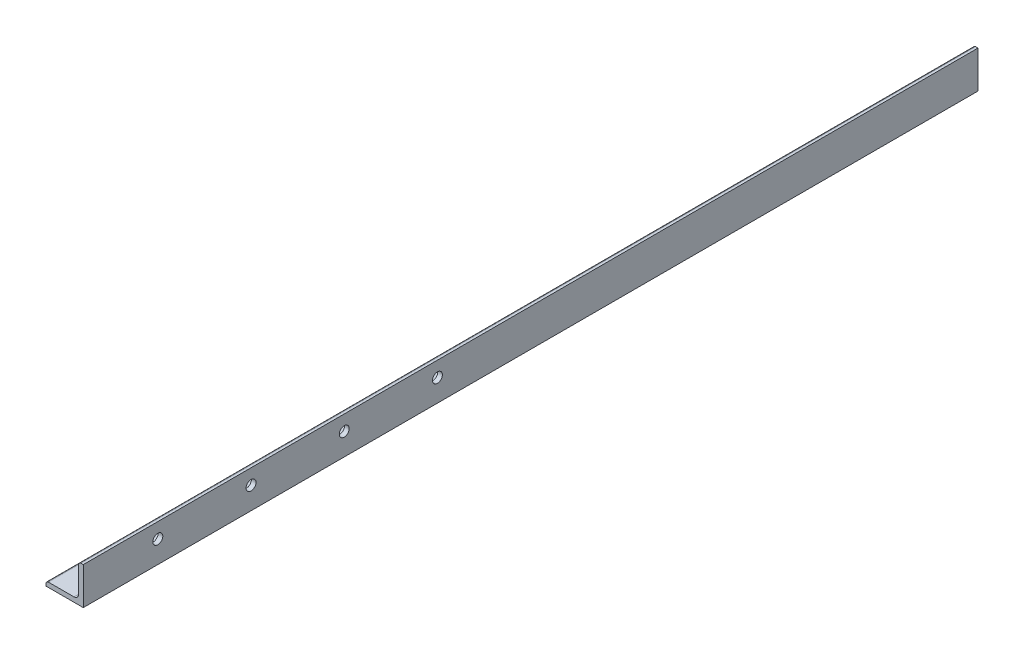
SolidWorks part; units mm, degrees
material "6061-T6 (SS)"
ref_plane "Front Plane" through (0, 0, 0) normal (0, 0, 1) x (1, 0, 0)
ref_plane "Top Plane" through (0, 0, 0) normal (0, 1, 0) x (1, 0, 0)
ref_plane "Right Plane" through (0, 0, 0) normal (1, 0, 0) x (0, 0, -1)
sketch "Sketch0" plane through (0, 0, 0) normal (0, 0, 1) x (1, 0, 0)
  line L0 (-12.7, -12.7) -> (12.7, -12.7)
  line L1 (12.7, -12.7) -> (12.7, 12.7)
  line L2 (12.7, 0) -> (0, 0) construction
  line L3 (0, 0) -> (0, -12.7) construction
  line L4 (9.525, -6.35) -> (9.525, 12.7) construction
  line L5 (6.35, -9.525) -> (-12.7, -9.525) construction
  arc A0 (9.525, -6.35) -> (6.35, -9.525) centre (6.35, -6.35) cw
  point P3 (8.5951, -8.5951)
  dimension "Inside Corner Radius" = 3.175
  dimension "Outside Height" = 25.4
  dimension "Inside Height" = 22.225
  dimension "Inside Width" = 22.225
  dimension "Wall Thickness" = 3.175
  dimension "D1" = 3.175
  dimension "Outside Width" = 25.4
sketch "Sketch1" plane through (0, 0, 0) normal (1, 0, 0) x (0, 0, -1)
  line L0 (304.8, 0) -> (-304.8, 0)
  point P4 (0, 0)
  dimension "Length" = 609.6
sketch "Sketch2" plane through (0, 0, 0) normal (0, 0, 1) x (1, 0, 0)
  line L0 (-12.7, -12.7) -> (12.7, -12.7)
  line L1 (12.7, -12.7) -> (12.7, 12.7)
  line L2 (12.7, 12.7) -> (9.525, 12.7) construction
  line L3 (9.525, 11.1125) -> (9.525, -6.35)
  line L4 (6.35, -9.525) -> (-11.1125, -9.525)
  line L5 (-12.7, -12.7) -> (-12.7, -9.525) construction
  line L6 (11.1125, 12.7) -> (12.7, 12.7)
  line L7 (-12.7, -11.1125) -> (-12.7, -12.7)
  line L8 (12.7, 0) -> (0, 0) construction
  line L9 (0, 0) -> (0, -12.7) construction
  arc A0 (9.525, 11.1125) -> (11.1125, 12.7) centre (11.1125, 11.1125) cw
  arc A1 (-12.7, -11.1125) -> (-11.1125, -9.525) centre (-11.1125, -11.1125) cw
  arc A2 (9.525, -6.35) -> (6.35, -9.525) centre (6.35, -6.35) cw
  dimension "Inside Radius" = 3.175
  dimension "Height" = 25.4
  dimension "Width" = 25.4
  dimension "Thickness" = 3.175
extrude "Boss-Extrude1" add sketch "Sketch2" along normal mid plane 609.6
sketch "Break Locations" plane through (0, 0, 0) normal (1, 0, 0) x (0, 0, -1)
  line L0 (-278.892, 0) -> (278.892, 0)
  line L1 (-304.8, -12.7) -> (-304.8, 12.7) construction
  line L2 (304.8, -12.7) -> (304.8, 12.7) construction
  point P0 (-283.21, 0)
  point P1 (283.21, 0)
  point P10 (0, 0)
  point P11 (278.892, 0)
  point P13 (-278.892, 0)
  dimension "D1" = 21.59
  dimension "D2" = 21.59
  dimension "D3" = 25.908
hole_wizard "1/4 Clearance Hole1" positions "Sketch3" profile "Sketch4" hole size "1/4" standard "ANSI Inch" end condition through all
sketch "Sketch3" plane through (0, -9.525, 0) normal (0, 1, 0) x (-1, 0, 0)
  line L0 (-6.35, 304.8) -> (11.1125, 304.8) construction
  line L1 (-6.35, -304.8) -> (11.1125, -304.8) construction
  point P0 (2.3812, 282.575)
  point P4 (2.3812, -228.6)
  point P9 (2.3812, 304.8)
  point P12 (2.3812, 105.9688)
  dimension "D1" = 176.6062
  dimension "D2" = 22.225
  dimension "D3" = 76.2
sketch "Sketch4" plane through (-2.3812, -9.525, 282.575) normal (1, 0, 0) x (0, 0, 1)
  line L0 (0, 0) -> (0, 3.175)
  line L1 (0, 3.175) -> (3.3782, 3.175)
  line L2 (3.3782, 3.175) -> (3.3782, 0)
  line L5 (3.3782, 0) -> (0, 0)
  line L11 (0, -6.35) -> (0, 107.95) construction
  dimension "Thru Hole Dia." = 6.7564
  dimension "Thru Hole Depth" = 3.175
hole_wizard "1/4 Clearance Hole2" positions "Sketch5" profile "Sketch6" hole size "1/4" standard "ANSI Inch" end condition through all
sketch "Sketch5" plane through (9.525, 0, 0) normal (-1, 0, 0) x (0, 0, 1)
  line L0 (304.8, 11.1125) -> (304.8, -6.35) construction
  point P0 (254, 2.3812)
  point P2 (190.5, 2.3812)
  point P4 (127, 2.3812)
  point P6 (63.5, 2.3812)
  point P13 (304.8, 2.3812)
  dimension "D1" = 50.8
  dimension "D2" = 63.5
  dimension "D3" = 63.5
  dimension "D4" = 63.5
sketch "Sketch6" plane through (9.525, 2.3813, 254) normal (0, 1, 0) x (0, 0, 1)
  line L0 (0, 0) -> (0, 3.175)
  line L1 (0, 3.175) -> (3.3782, 3.175)
  line L2 (3.3782, 3.175) -> (3.3782, 0)
  line L5 (3.3782, 0) -> (0, 0)
  line L11 (0, -6.35) -> (0, 107.95) construction
  dimension "Thru Hole Dia." = 6.7564
  dimension "Thru Hole Depth" = 3.175
sketch "Sketch7" plane through (9.525, 0, 0) normal (-1, 0, 0) x (0, 0, 1)
  line L0 (-304.8, -6.35) -> (-254, 12.7)
  line L1 (304.8, 12.7) -> (-304.8, 12.7) construction
  line L2 (-254, 12.7) -> (-304.8, 12.7)
  line L3 (-304.8, 12.7) -> (-304.8, -6.35)
  dimension "D1" = 50.8
extrude "Cut-Extrude1" [suppressed] cut sketch "Sketch7" against normal through all
hole_wizard "5/16 Clearance Hole1" positions "Sketch8" profile "Sketch9" hole size "5/16" standard "ANSI Inch" end condition through all
sketch "Sketch8" plane through (0, -9.525, 0) normal (0, 1, 0) x (1, 0, 0)
  line L0 (-2.3813, 279.4) -> (-2.3812, 228.6) construction
  point P0 (-2.3813, 279.4)
  dimension "D1" = 50.8
sketch "Sketch9" plane through (-2.3813, -9.525, -279.4) normal (1, 0, 0) x (0, 0, 1)
  line L0 (0, 0) -> (0, 3.175)
  line L1 (0, 3.175) -> (4.2164, 3.175)
  line L2 (4.2164, 3.175) -> (4.2164, 0)
  line L5 (4.2164, 0) -> (0, 0)
  line L11 (0, -6.35) -> (0, 107.95) construction
  dimension "Thru Hole Dia." = 8.4328
  dimension "Thru Hole Depth" = 3.175
equation "\"D1@Break Locations\" = .85 * \"Height@Sketch2\""
equation "\"D2@Break Locations\"=\"D1@Break Locations\""
equation "\"Thickness@Sketch2\"=\"wall thickness@sketch0\""
equation "\"Height@Sketch2\"=\"outside height@sketch0\""
equation "\"Width@Sketch2\"=\"outside width@sketch0\""
equation "\"Inside Radius@Sketch2\"=\"inside corner radius@sketch0\""
equation "\"Length@Boss-Extrude1\"=24"
equation "\"D3@Break Locations\"=\"D2@Break Locations\"*1.2"
equation "\"D1@Sketch0\"=\"Wall Thickness@Sketch0\""
